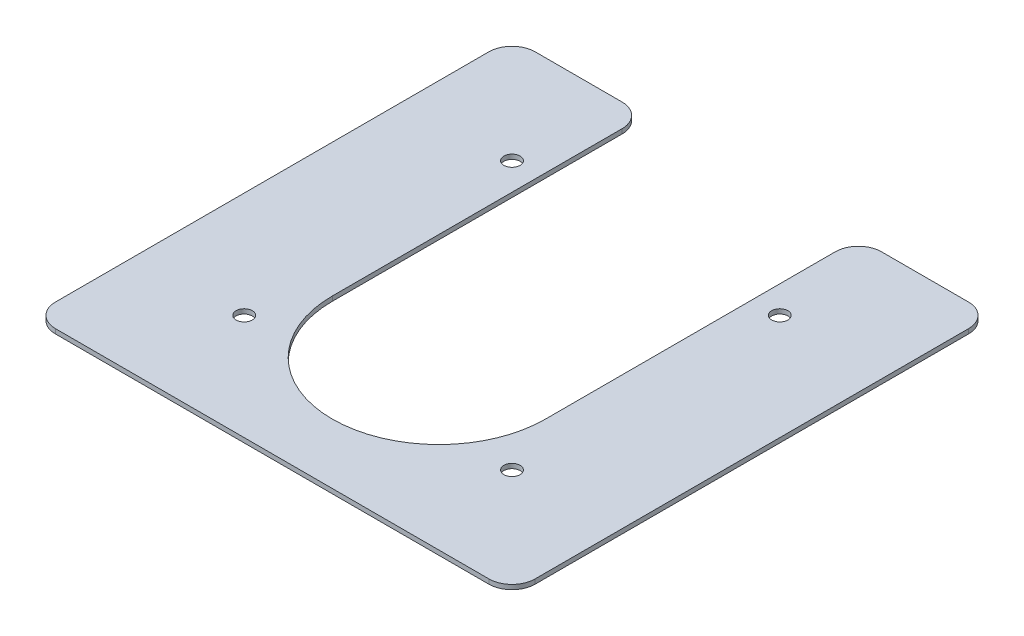
SolidWorks part; units mm, degrees
ref_plane "Front Plane" through (0, 0, 0) normal (0, 0, 1) x (1, 0, 0)
ref_plane "Top Plane" through (0, 0, 0) normal (0, 1, 0) x (1, 0, 0)
ref_plane "Right Plane" through (0, 0, 0) normal (1, 0, 0) x (0, 0, -1)
sketch "Sketch1" plane through (0, 0, 0) normal (0, 1, 0) x (1, 0, 0)
  line L0 (0, 0) -> (0, 21) construction
  line L1 (51.8722, -39.9014) -> (51.8722, 63.843) construction
  line L3 (51.8722, 63.843) -> (-51.8722, 63.843) construction
  line L4 (-51.8722, 63.843) -> (-51.8722, -39.9014) construction
  line L5 (51.8722, -34.9014) -> (51.8722, 58.843)
  line L6 (-46.8722, -39.9014) -> (46.8722, -39.9014)
  line L7 (51.8722, 63.843) -> (-51.8722, 63.843) construction
  line L8 (-51.8722, 58.843) -> (-51.8722, -34.9014)
  line L10 (36.8722, -39.9014) -> (36.8722, 63.843) construction
  line L11 (-36.8722, -39.9014) -> (-36.8722, 63.843) construction
  line L12 (36.8722, -39.9014) -> (36.8722, 63.843) construction
  line L13 (-36.8722, -39.9014) -> (-36.8722, 63.843) construction
  line L14 (23.0585, -3.843) -> (23.0585, 58.843)
  line L15 (-23.0585, -3.843) -> (-23.0585, 58.843)
  line L16 (-46.8722, 63.843) -> (-28.0585, 63.843)
  line L17 (28.0585, 63.843) -> (46.8722, 63.843)
  circle A0 centre (0, 0) radius 21 construction
  circle A1 centre (0, 0) radius 21 construction
  circle A2 centre (28.9653, -16.9946) radius 1.75 construction
  circle A3 centre (-28.9653, -16.9946) radius 1.75 construction
  circle A4 centre (28.9653, 40.9361) radius 1.75 construction
  circle A5 centre (-28.9653, 40.9361) radius 1.75 construction
  circle A6 centre (28.9653, -16.9946) radius 1.75
  circle A7 centre (-28.9653, -16.9946) radius 1.75
  circle A8 centre (28.9653, 40.9361) radius 1.75
  circle A9 centre (-28.9653, 40.9361) radius 1.75
  circle A10 centre (0, -3.843) radius 21.0585 construction
  arc A11 (-21.0585, -3.843) -> (21.0585, -3.843) centre (0, -3.843) ccw construction
  arc A12 (-23.0585, -3.843) -> (23.0585, -3.843) centre (0, -3.843) ccw
  arc A13 (28.0585, 63.843) -> (23.0585, 58.843) centre (28.0585, 58.843) ccw
  circle A14 centre (0, -3.843) radius 23.0585 construction
  arc A15 (-28.0585, 63.843) -> (-23.0585, 58.843) centre (-28.0585, 58.843) cw
  arc A16 (46.8722, 63.843) -> (51.8722, 58.843) centre (46.8722, 58.843) cw
  arc A17 (51.8722, -34.9014) -> (46.8722, -39.9014) centre (46.8722, -34.9014) cw
  arc A18 (-46.8722, -39.9014) -> (-51.8722, -34.9014) centre (-46.8722, -34.9014) cw
  arc A19 (-51.8722, 58.843) -> (-46.8722, 63.843) centre (-46.8722, 58.843) cw
  point P39 (31.0585, -3.843)
  point P42 (23.0585, 63.843)
  point P45 (-23.0585, 63.843)
  dimension "D1" = 2
  dimension "D2" = 5
sketch "Sketch2" plane through (0, 0, 0) normal (0, 0, 1) x (1, 0, 0)
  line L1 (51.8722, -1) -> (-51.8722, -1)
  line L2 (51.8722, -1) -> (51.8722, 0)
  line L3 (51.8722, 0) -> (-51.8722, 0)
  line L4 (-51.8722, -1) -> (-51.8722, 0)
extrude "Boss-Extrude1" add sketch "Sketch1" against normal up to vertex (1 mm away) up to point (51.8722, -1, 0)
